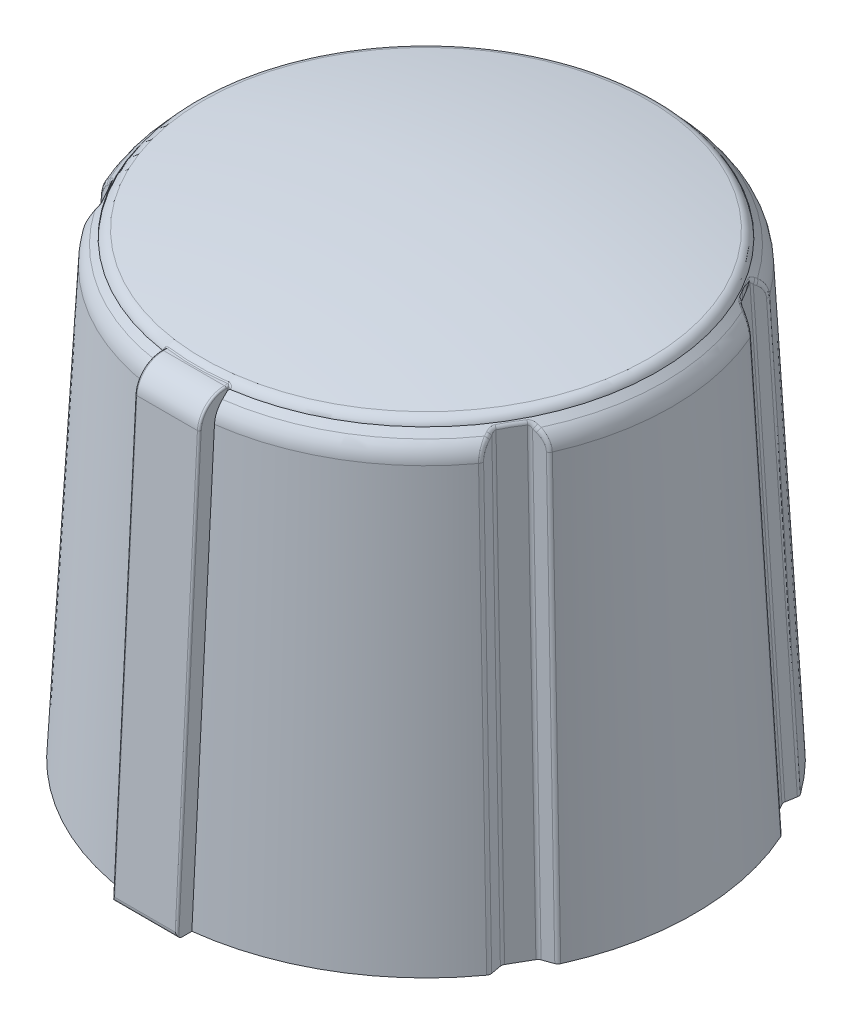
SolidWorks part; units mm, degrees
ref_plane "Front Plane" through (0, 0, 0) normal (0, 0, 1) x (1, 0, 0)
ref_plane "Top Plane" through (0, 0, 0) normal (0, 1, 0) x (1, 0, 0)
ref_plane "Right Plane" through (0, 0, 0) normal (1, 0, 0) x (0, 0, -1)
sketch "Sketch1" plane through (0, 0, 0) normal (0, 0, 1) x (1, 0, 0)
  line L0 (0, 8.89) -> (0, -8.89) construction
  line L1 (0, -8.89) -> (-9.97, -8.89) construction
  line L2 (-9.97, -8.89) -> (-9.5041, 0) construction
  line L3 (-3.4, -8.89) -> (-3, -8.49)
  line L4 (-3, -8.49) -> (-3, 6.35)
  line L5 (-3, 6.35) -> (3, 6.35)
  line L6 (3, 6.35) -> (3, -8.49)
  line L7 (3, -8.49) -> (3.4, -8.89)
  arc A0 (3, -3.3713) -> (3, -4.2487) centre (3.26, -3.81) ccw
  point P3 (-3, -8.89)
  point P4 (0, 0)
  point P6 (0, 6.35)
  point P7 (3, -8.89)
  point P11 (-7.94, -8.89)
  point P17 (7.94, -8.89)
  point P19 (0, -6.35)
  point P23 (2.75, -3.81)
  dimension "D4" = 0.51
  dimension "Head Height" = 17.78
  dimension "Head Diameter" = 19.94
  dimension "Hole Depth" = 15.24
  dimension "Taper" = 3
  dimension "Hole Diameter" = 6
  dimension "D1" = 45
  dimension "D3" = 0.25
  dimension "D5" = 5.08
  dimension "Counterbore Diamter" = 15.88
  dimension "D6" = 2.54
sketch "Sketch2" plane through (0, 0, 0) normal (0, 1, 0) x (1, 0, 0)
  line L0 (3, 0) -> (-3, 0) construction
  line L1 (0, 0) -> (-9.97, 0) construction
  line L2 (-2.5981, 1.5) -> (2.5981, 1.5)
  circle A0 centre (0, 0) radius 3
  circle A1 centre (0, 0) radius 9.97
  point P6 (0, 0)
  point P13 (0, 3)
  point P14 (0, -3)
  dimension "D1" = 4.5
sketch "Sketch3" plane through (0, 0, 0) normal (0, 0, 1) x (1, 0, 0)
  line L0 (0, 8.89) -> (0, -8.89) construction
  line L1 (0, -8.89) -> (-9.97, -8.89)
  line L2 (-9.97, -8.89) -> (-9.1369, 7.0067)
  line L3 (-8.8454, 7.6614) -> (-8.6168, 7.89)
  line L4 (-8.6168, 7.89) -> (0, 7.89)
  line L5 (0, -8.89) -> (0, 7.89)
  line L6 (-9.97, -8.89) -> (-9.5041, 0) construction
  arc A0 (-9.1369, 7.0067) -> (-8.8454, 7.6614) centre (-8.1383, 6.9543) cw
  point P11 (-9.1168, 7.39)
  dimension "D5" = 1
  dimension "D1" = 1
  dimension "D3" = 45
  dimension "D4" = 0.5
revolve "Revolve1" add sketch "Sketch3" angle 360 about L0
sketch "Sketch6" plane through (0, 0, 0) normal (1, 0, 0) x (0, 0, -1)
  line L1 (1.5, -3.3713) -> (1.5, -4.2487)
  line L3 (-9.1369, 7.0067) -> (-9.97, -8.89) construction
  line L4 (-9.1369, 7.0067) -> (-9.97, -8.89) construction
  line L7 (-9.0518, 7.3611) -> (-9.1183, 7.3611) construction
  arc A0 (1.5, -3.3713) -> (1.5, -4.2487) centre (1.76, -3.81) ccw
  arc A1 (-8.8454, 7.6614) -> (-9.1369, 7.0067) centre (-8.1383, 6.9543) ccw construction
  arc A2 (-8.8454, 7.6614) -> (-9.1369, 7.0067) centre (-8.1383, 6.9543) ccw construction
  point P0 (1.25, -3.81)
  point P10 (-9.1183, 7.3611)
  dimension "D1" = 0.51
  dimension "D2" = 0.25
sketch "Sketch7" plane through (0, -8.89, 0) normal (0, -1, 0) x (1, 0, 0)
  line L0 (0, 0) -> (0, 9.97) construction
  line L1 (0.4985, 9.5712) -> (-0.4985, 9.5712)
  line L2 (-0.4985, 9.5712) -> (-0.9228, 9.9272)
  line L3 (0.4985, 9.5712) -> (0.9228, 9.9272)
  circle A0 centre (0, 0) radius 9.97 construction
  arc A1 (0.9228, 9.9272) -> (-0.9228, 9.9272) centre (0, 0) ccw
  point P10 (0, 9.5712)
  dimension "D1" = 0.3988
  dimension "D2" = 0.997
  dimension "D3" = 50
extrude "Cut-Extrude2" cut sketch "Sketch7" along direction (0, -0.9986, 0.0523) on the side against the normal through all
fillet "Fillet1" radius 0.1994 9 edges at (-0.8814, 7.2652, 9.0459) (0.8087, 7.4407, 8.9757) (0.4985, -0.5471, 9.134) (-0.4985, -0.5471, 9.134)
pattern_circular "CirPattern1" count 6 over 360 of "Cut-Extrude2", "Fillet1"
sketch "Sketch14" plane through (0, 7.89, 0) normal (0, 1, 0) x (1, 0, 0)
  circle A1 centre (0, 0) radius 8.6168
  circle A2 centre (0, 0) radius 8.6168
  dimension "D1" = 0
extrude "Cut-Extrude4" cut sketch "Sketch14" against normal through all draft 1.5 draft outward yes
sketch "Sketch8" plane through (0, 0, 0) normal (0, 0, 1) x (1, 0, 0)
  line L0 (-9.0562, -8.89) -> (9.0562, -8.89) construction
  line L3 (0, 8.89) -> (0, -8.89) construction
  line L4 (0, 8.89) -> (0, -8.89)
  line L5 (8.6168, 7.89) -> (8.6168, 8.09)
  line L6 (0, -8.89) -> (9.0562, -8.89)
  line L8 (8.6168, 7.89) -> (9.0562, -8.89)
  line L9 (8.6168, 7.89) -> (-8.6168, 7.89) construction
  line L10 (8.6168, 7.89) -> (-8.6168, 7.89) construction
  arc A1 (0, 8.89) -> (8.6168, 8.09) centre (0, -37.9158) cw
  dimension "D1" = 0.2
revolve "Revolve2" add sketch "Sketch8" angle 360 about L4
fillet "Fillet2" radius 0.4 1 edges at (-8.6168, 8.09, 0)
sketch "Sketch15" plane through (0, -8.89, 0) normal (0, -1, 0) x (1, 0, 0)
  line L1 (-1.1964, 9.97) -> (1.1964, 9.97)
  line L2 (-1.1964, 9.97) -> (-1.1964, 0)
  line L3 (-1.1964, 0) -> (1.1964, 0)
  line L4 (1.1964, 9.97) -> (1.1964, 0)
  circle A0 centre (0, 0) radius 9.97 construction
  point P4 (0, 0)
  dimension "D1" = 2.3928
extrude "Cut-Extrude5" cut sketch "Sketch15" against normal through all
sketch "Sketch16" plane through (0, -8.89, 0) normal (0, -1, 0) x (1, 0, 0)
  line L0 (-1.1964, 9.5712) -> (1.1964, 9.5712)
  line L4 (1.1964, 9.97) -> (-1.1964, 9.97)
  line L5 (1.1964, 0) -> (1.1964, 9.97)
  line L6 (-1.1964, 0) -> (1.1964, 0)
  line L7 (-1.1964, 9.97) -> (-1.1964, 0)
  line L9 (1.1964, 0) -> (1.1964, 9.5712)
  line L10 (-1.1964, 0) -> (1.1964, 0)
  line L11 (-1.1964, 9.5712) -> (-1.1964, 0)
  dimension "D2" = 9.5712
extrude "Boss-Extrude2" add sketch "Sketch16" against normal blind 16.891
draft "Draft1" type of draft neutral plane draft angle 3 faces to draft 1 face at (0, -0.4445, 9.5712) neutral plane through (0, 8.001, 0) neutral plane normal (0, 1, 0) parameters "D1"=3
fillet "Fillet5" radius 1 1 edges at (0, 8.001, 9.5712)
fillet "Fillet6" radius 0.07 11 edges at (1.1964, 7.8697, 8.5201) (1.1964, 8.001, 8.5372) (1.1964, -0.9183, 10.0386) (-1.1964, -0.9183, 10.0386) (-1.1964, 8.001, 8.5372) (0, 8.001, 8.5365) (1.1964, 7.7264, 9.3106) (-1.1964, 7.7264, 9.3106)
fillet "Fillet7" radius 0.08 2 edges
fillet "Fillet9" radius 0.2 1 edges at (0, -8.89, 10.4564)
sketch "Sketch13" plane through (0, -8.89, 0) normal (0, -1, 0) x (1, 0, 0)
  line L2 (-2.5981, -1.5) -> (2.5981, -1.5) construction
  line L3 (-2.5981, -1.5) -> (2.5981, -1.5)
  circle A2 centre (0, 0) radius 3 construction
  arc A3 (2.5981, -1.5) -> (-2.5981, -1.5) centre (0, 0) ccw
extrude "Cut-Extrude3" cut sketch "Sketch13" against normal up to vertex (15.24 mm away) up to point (0, 6.35, 0)
sketch "Sketch17" plane through (0, -8.89, 0) normal (0, -1, 0) x (1, 0, 0)
  circle A0 centre (0, 0) radius 7.94
extrude "Cut-Extrude6" cut sketch "Sketch17" against normal up to vertex (2.54 mm away) up to point (0, -6.35, 0)
extrude "Boss-Extrude3" add sketch "Sketch6" against normal up to surface and the other way up to surface up to face at (0, 0, 0.75) other way up to face at (0, 0, 0.75)
fillet "Fillet8" radius 0.05 3 edges at (-2.7269, -3.7869, -1.2505) (0, -4.2487, -1.5) (2.7269, -3.7869, -1.2505)
fillet "Fillet10" radius 0.4 2 edges at (7.94, -8.89, 0) (7.94, -6.35, 0)
fillet "Fillet11" radius 0.2 2 edges at (0, -6.35, -1.5) (0, -6.35, 3)
sketch "Sketch11" plane through (0, -8.89, 0) normal (0, -1, 0) x (1, 0, 0)
  line L1 (-2.5981, -1.5) -> (2.5981, -1.5) construction
  line L2 (-2.5981, -1.5) -> (2.5981, -1.5)
  circle A0 centre (0, 0) radius 3 construction
  circle A3 centre (0, 0) radius 9.97 construction
  circle A4 centre (0, 0) radius 9.97
  arc A5 (2.5981, -1.5) -> (-2.5981, -1.5) centre (0, 0) ccw
  point P3 (-3, 0)
  point P4 (3, 0)
  point P7 (-9.97, 0)
  point P10 (9.97, 0)
sketch "Sketch12" plane through (0, 0, 0) normal (1, 0, 0) x (0, 0, -1)
  line L0 (-10.4564, -8.89) -> (-10.3162, -8.89) construction
  line L1 (-10.4564, -8.89) -> (-10.3162, -8.89)
  line L3 (-3, -8.89) -> (-3, 6.35)
  line L4 (-3, 6.35) -> (1.5, 6.35)
  line L5 (1.5, 6.35) -> (1.5, -8.89)
  line L7 (-3, -8.89) -> (1.5, -8.89)
  line L8 (9.97, 0) -> (-9.97, 0) construction
  line L9 (9.97, 0) -> (-9.97, 0) construction
  point P4 (9.97, -8.89)
  point P5 (-9.97, 8.89)
  point P6 (0, 8.89)
  point P14 (1.5, 6.35)
  point P15 (-10.4564, -8.89)
equation "\"D1@Sketch7\"= \"Head Diameter@Sketch1\" * .02"
equation "\"D2@Sketch7\" = \"Head Diameter@Sketch1\" * .05"
equation "\"D1@Fillet1\"=\"Head Diameter@Sketch1\" * .01"
equation "\"D1@Sketch15\" = \"Head Diameter@Sketch1\" * .12"
equation "\"D2@Sketch16\" = \"Head Diameter@Sketch1\" * .48"
equation "\"D1@Boss-Extrude2\" = \"Head Height@Sketch1\" * .95"
equation "\"D1@Sketch6\"=\"D4@Sketch1\""
equation "\"D2@Sketch6\"=\"D3@Sketch1\""
